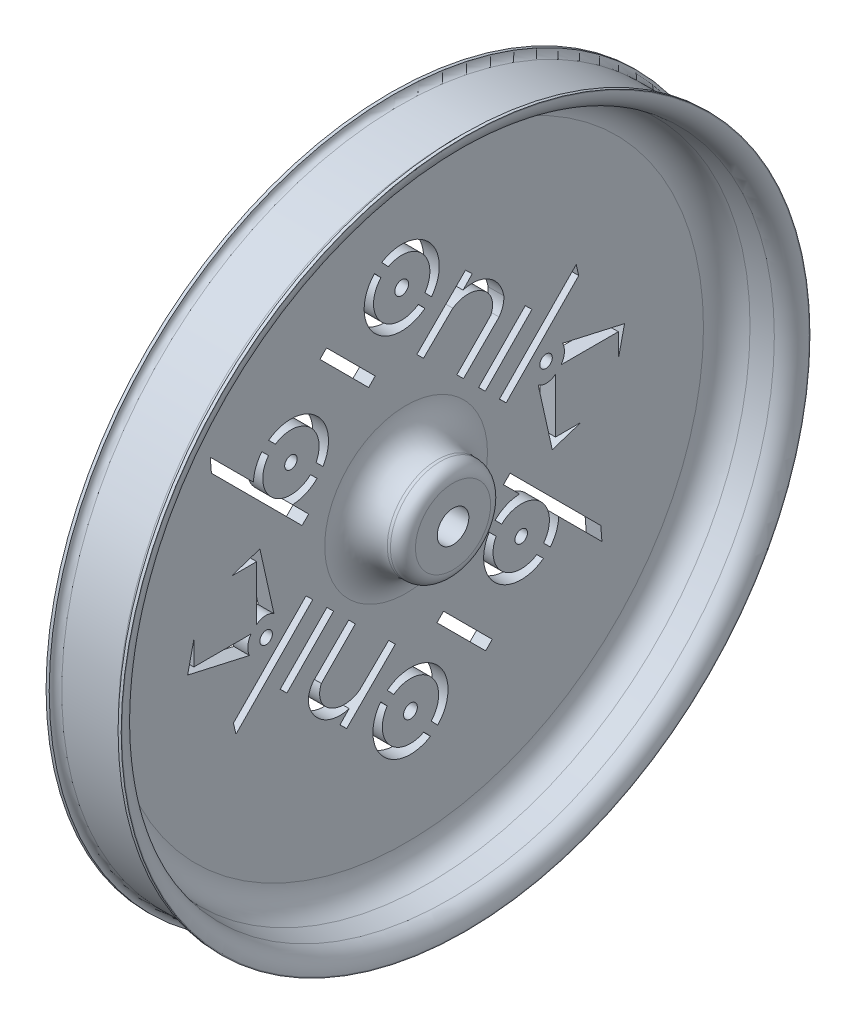
SolidWorks part; units mm, degrees
ref_plane "Płaszczyzna przednia" through (0, 0, 0) normal (0, 0, 1) x (1, 0, 0)
ref_plane "Płaszczyzna górna" through (0, 0, 0) normal (0, 1, 0) x (1, 0, 0)
ref_plane "Płaszczyzna prawa" through (0, 0, 0) normal (1, 0, 0) x (0, 0, -1)
sketch "Szkic1" plane through (0, 0, 0) normal (0, 0, 1) x (1, 0, 0)
  line L0 (7.5, -25.7789) -> (-2.5, -25.7789)
  line L1 (7.5, -25.7789) -> (7.5, -17.7789)
  line L2 (7.5, -17.7789) -> (0, -17.7789)
  line L3 (0, -17.7789) -> (0, 21.719)
  line L4 (-2.5, 29.2211) -> (-2, 29.2211)
  line L5 (9.5, 29.2211) -> (9.5, 29.1143)
  line L6 (9.5, 29.2211) -> (9, 29.2211)
  line L7 (-2, 29.2211) -> (-2, 29.2183)
  line L8 (-1, 28.2183) -> (8, 28.2183)
  line L9 (-2.5, 29.2211) -> (-2.5, -25.7789)
  line L10 (3.4713, 25.6839) -> (6.8965, 26.1406)
  line L11 (9, 29.2183) -> (9, 29.2211)
  arc A0 (-1, 28.2183) -> (-2, 29.2183) centre (-1, 29.2183) cw
  arc A1 (9.5, 29.1143) -> (6.8965, 26.1406) centre (6.5, 29.1143) cw
  arc A2 (0, 21.719) -> (3.4713, 25.6839) centre (4, 21.719) cw
  arc A3 (8, 28.2183) -> (9, 29.2183) centre (8, 29.2183) ccw
  point P10 (9.5, 26.2211)
  point P17 (0, 27.2211)
  dimension "D6" = 0.5
  dimension "D9" = 3
  dimension "D10" = 4
  dimension "D12" = 1
  dimension "D1" = 10
  dimension "D2" = 8
  dimension "D3" = 55
  dimension "D4" = 12
  dimension "D5" = 3
  dimension "D7" = 0.5
  dimension "D8" = 45
  dimension "D11" = 2.5
revolve "Obrót1" add sketch "Szkic1" angle 360 about L0
sketch "Szkic4" plane through (7.5, 0, 0) normal (1, 0, 0) x (0, 0, -1)
  circle A0 centre (0, -25.7789) radius 2.525
  dimension "D1" = 5.05
extrude "Wytnij-wyciągnięcie8" cut sketch "Szkic4" against normal through all
sketch "Szkic5" plane through (0, 0, 0) normal (1, 0, 0) x (0, 0, -1)
  line L0 (112.1629, 275.1146) -> (679.4962, 275.1146) construction
  line L1 (-31.0948, -6.6131) -> (-16.6157, -21.0922)
  line L2 (-16.6157, -21.0922) -> (-15.5551, -20.0316)
  line L3 (-15.5551, -20.0316) -> (-18.1257, -17.4609)
  line L4 (-24.3831, -11.2036) -> (-31.2774, -4.3092)
  line L5 (-31.2774, -4.3092) -> (-31.0948, -6.6131)
  line L6 (-13.7626, 0.4627) -> (-12.702, 1.5234)
  line L7 (-12.702, 1.5234) -> (-4.9238, -6.2548)
  line L8 (-4.9238, -6.2548) -> (-5.9844, -7.3154)
  line L9 (-5.9844, -7.3154) -> (-13.7626, 0.4627)
  line L10 (2.7778, -7.6585) -> (1.7172, -6.5979)
  line L11 (1.7172, -6.5979) -> (9.4953, 1.1803)
  line L12 (9.4953, 1.1803) -> (10.57, 0.1339)
  line L13 (10.57, 0.1339) -> (9.0927, -1.3833)
  line L14 (2.7778, -7.6585) -> (7.4664, -3.0724)
  line L15 (14.8516, -7.9843) -> (9.168, -13.6679)
  line L16 (9.168, -13.6679) -> (8.1073, -12.6072)
  line L17 (8.1073, -12.6072) -> (13.5313, -7.0832)
  line L18 (19.0342, -8.5077) -> (20.1045, -9.5586)
  line L19 (20.1045, -9.5586) -> (12.6512, -17.1495)
  line L20 (12.6512, -17.1495) -> (11.5808, -16.0986)
  line L21 (11.5808, -16.0986) -> (19.0342, -8.5077)
  line L22 (14.91, -19.3675) -> (27.173, -6.8781)
  line L23 (27.173, -6.8781) -> (27.5713, -8.6134)
  line L24 (27.5713, -8.6134) -> (15.9803, -20.4184)
  line L25 (15.9803, -20.4184) -> (14.91, -19.3675)
  line L30 (25.0179, -16.6923) -> (34.8909, -18.9183)
  line L31 (34.8909, -18.9183) -> (33.8934, -23.3427)
  line L32 (33.8934, -23.3427) -> (33.8934, -19.5403)
  line L33 (33.8934, -19.5403) -> (24.7607, -19.5403)
  line L34 (21.1025, -20.5215) -> (23.3499, -30.5953)
  line L35 (23.3499, -30.5953) -> (27.9255, -29.0986)
  line L36 (27.9255, -29.0986) -> (23.865, -29.0986)
  line L37 (23.865, -29.0986) -> (23.865, -20.3921)
  line L38 (-14.2148, -15.7768) -> (-15.2757, -14.716)
  line L39 (-13.2714, -14.599) -> (-14.3731, -13.4973)
  line L40 (-21.9663, -8.7368) -> (-23.0341, -7.669)
  line L41 (-20.8696, -7.7122) -> (-21.9465, -6.6352)
  line L42 (-2.824, 7.8162) -> (-3.8882, 8.9319)
  line L43 (-4.0153, 6.8919) -> (-5.0523, 7.9791)
  line L44 (3.009, 1.3009) -> (4.0611, 0.1978)
  line L45 (1.9645, 0.2227) -> (3.0062, -0.8694)
  arc A0 (-2.824, 7.8162) -> (3.009, 1.3009) centre (-0.7, 3.8491) cw
  circle A1 centre (-18.3888, -11.4667) radius 1
  arc A2 (-4.0153, 6.8919) -> (1.9645, 0.2227) centre (-0.7, 3.8491) ccw
  circle A3 centre (-0.7, 3.8491) radius 1.1
  arc A6 (7.4664, -3.0724) -> (12.8569, -3.5397) centre (9.8742, -6.6212) cw
  arc A7 (9.0927, -1.3833) -> (15.6101, -5.4316) centre (10.5698, -6.2757) cw
  arc A8 (12.8569, -3.5397) -> (13.5313, -7.0832) centre (10.6785, -5.7902) cw
  arc A9 (15.6101, -5.4316) -> (14.8516, -7.9843) centre (11.6962, -5.6576) cw
  circle A10 centre (22.3514, -17.8482) radius 1
  arc A11 (25.0179, -16.6923) -> (24.7607, -19.5403) centre (22.4645, -17.8973) cw
  arc A12 (23.865, -20.3921) -> (21.1025, -20.5215) centre (22.3975, -18.6134) cw
  arc A13 (-23.0341, -7.669) -> (-24.3831, -11.2036) centre (-18.3888, -11.4667) ccw
  arc A14 (-21.9465, -6.6352) -> (-13.2714, -14.599) centre (-18.3888, -11.4667) cw
  arc A15 (-14.3731, -13.4973) -> (-20.8696, -7.7122) centre (-18.3888, -11.4667) ccw
  arc A16 (-21.9663, -8.7368) -> (-15.2757, -14.716) centre (-18.3888, -11.4667) ccw
  arc A17 (-14.2148, -15.7768) -> (-18.1257, -17.4609) centre (-18.3888, -11.4667) cw
  arc A18 (-3.8882, 8.9319) -> (4.0611, 0.1978) centre (-0.7, 3.8491) cw
  arc A19 (-5.0523, 7.9791) -> (3.0062, -0.8694) centre (-0.7, 3.8491) ccw
  point P71 (-1, -15)
  dimension "D11" = 1.5
  dimension "D12" = 2
  dimension "D13" = 2
  dimension "D14" = 1.5
  dimension "D15" = 1.5
  dimension "D19" = 11
  dimension "D23" = 1.5
  dimension "D24" = 1.5
  dimension "D25" = 6
  dimension "D26" = 6
  dimension "D1" = 1.5
  dimension "D2" = 1.5
  dimension "D5" = 1.5
  dimension "D6" = 1.5
  dimension "D7" = 1.5
  dimension "D8" = 1.5
  dimension "D9" = 1.5
  dimension "D10" = 1.5
  dimension "D16" = 1.5
  dimension "D17" = 1.5
  dimension "D18" = 1.5
  dimension "D20" = 11
  dimension "D21" = 10.6384
  dimension "D22" = 1.5
  dimension "D27" = 0.524
extrude "Wytnij-wyciągnięcie9" cut sketch "Szkic5" against normal through all
fillet "Zaokrąglenie1" radius 2 1 edges at (7.5, -25.7789, -8)
sketch "Szkic6" plane through (0, 0, 0) normal (1, 0, 0) x (0, 0, -1)
  line L35 (-20.6685, -60.7541) -> (-20.6685, -65.2374)
  line L36 (-20.6685, -65.2374) -> (-19.6852, -65.2374)
  line L37 (-19.6852, -65.2374) -> (-19.6852, -62.7584)
  line L38 (-19.729, -61.5951) -> (-19.6986, -61.5951)
  line L39 (-19.5465, -62.2204) -> (-18.3908, -65.2374)
  line L40 (-18.3908, -65.2374) -> (-17.4985, -65.2374)
  line L41 (-17.4985, -65.2374) -> (-16.3631, -62.1893)
  line L42 (-16.211, -61.5951) -> (-16.184, -61.5951)
  line L43 (-16.2244, -62.5549) -> (-16.2244, -65.2374)
  line L44 (-16.2244, -65.2374) -> (-15.1462, -65.2374)
  line L45 (-15.1462, -65.2374) -> (-15.1462, -60.7541)
  line L46 (-15.1462, -60.7541) -> (-16.7043, -60.7541)
  line L47 (-16.7043, -60.7541) -> (-17.6946, -63.4053)
  line L48 (-17.8871, -64.0525) -> (-17.9075, -64.0525)
  line L49 (-18.08, -63.4117) -> (-19.0699, -60.7541)
  line L50 (-19.0699, -60.7541) -> (-20.6685, -60.7541)
  line L51 (-12.801, -60.7541) -> (-14.565, -65.2374)
  line L52 (-14.565, -65.2374) -> (-13.3822, -65.2374)
  line L53 (-13.3822, -65.2374) -> (-13.041, -64.2401)
  line L54 (-13.041, -64.2401) -> (-11.3174, -64.2401)
  line L55 (-11.3174, -64.2401) -> (-10.9726, -65.2374)
  line L56 (-10.9726, -65.2374) -> (-9.7831, -65.2374)
  line L57 (-9.7831, -65.2374) -> (-11.5066, -60.7541)
  line L58 (-11.5066, -60.7541) -> (-12.801, -60.7541)
  line L59 (-8.7022, -60.7541) -> (-7.2894, -62.9959)
  line L60 (-7.2894, -62.9959) -> (-8.8338, -65.2374)
  line L61 (-8.8338, -65.2374) -> (-7.5327, -65.2374)
  line L62 (-7.5327, -65.2374) -> (-6.6945, -63.79)
  line L63 (-6.5829, -63.4774) -> (-6.5695, -63.4774)
  line L64 (-6.4716, -63.7776) -> (-5.6367, -65.2374)
  line L65 (-5.6367, -65.2374) -> (-4.3423, -65.2374)
  line L66 (-4.3423, -65.2374) -> (-5.8363, -62.9771)
  line L67 (-5.8363, -62.9771) -> (-4.3828, -60.7541)
  line L68 (-4.3828, -60.7541) -> (-5.5996, -60.7541)
  line L69 (-5.5996, -60.7541) -> (-6.37, -62.0859)
  line L70 (-6.5221, -62.4768) -> (-6.5358, -62.4768)
  line L71 (-6.6812, -62.0987) -> (-7.374, -60.7541)
  line L72 (-7.374, -60.7541) -> (-8.7022, -60.7541)
  line L73 (-2.5549, -60.7541) -> (-2.5549, -65.2374)
  line L74 (-2.5549, -65.2374) -> (-0.693, -65.2374)
  line L75 (-0.0506, -62.8302) -> (-0.0506, -62.8177)
  line L76 (-0.7909, -60.7541) -> (-2.5549, -60.7541)
  line L77 (4.4336, -60.7541) -> (2.6693, -65.2374)
  line L78 (2.6693, -65.2374) -> (3.8521, -65.2374)
  line L79 (3.8521, -65.2374) -> (4.1936, -64.2401)
  line L80 (4.1936, -64.2401) -> (5.9172, -64.2401)
  line L81 (5.9172, -64.2401) -> (6.2618, -65.2374)
  line L82 (6.2618, -65.2374) -> (7.4516, -65.2374)
  line L83 (7.4516, -65.2374) -> (5.728, -60.7541)
  line L84 (5.728, -60.7541) -> (4.4336, -60.7541)
  line L85 (8.877, -60.7541) -> (8.877, -63.3429)
  line L86 (12.8853, -63.2961) -> (12.8853, -60.7541)
  line L87 (12.8853, -60.7541) -> (11.7937, -60.7541)
  line L88 (11.7937, -60.7541) -> (11.7937, -63.3928)
  line L89 (9.9723, -63.3554) -> (9.9723, -60.7541)
  line L90 (9.9723, -60.7541) -> (8.877, -60.7541)
  line L91 (14.9702, -60.7541) -> (14.9702, -65.2374)
  line L92 (14.9702, -65.2374) -> (15.9537, -65.2374)
  line L93 (15.9537, -65.2374) -> (15.9537, -62.7584)
  line L94 (15.9096, -61.5951) -> (15.9401, -61.5951)
  line L95 (16.0921, -62.2204) -> (17.2482, -65.2374)
  line L96 (17.2482, -65.2374) -> (18.1402, -65.2374)
  line L97 (18.1402, -65.2374) -> (19.2759, -62.1893)
  line L98 (19.4279, -61.5951) -> (19.455, -61.5951)
  line L99 (19.4142, -62.5549) -> (19.4142, -65.2374)
  line L100 (19.4142, -65.2374) -> (20.4924, -65.2374)
  line L101 (20.4924, -65.2374) -> (20.4924, -60.7541)
  line L102 (20.4924, -60.7541) -> (18.9343, -60.7541)
  line L103 (18.9343, -60.7541) -> (17.9443, -63.4053)
  line L104 (17.7515, -64.0525) -> (17.7314, -64.0525)
  line L105 (17.559, -63.4117) -> (16.5687, -60.7541)
  line L106 (16.5687, -60.7541) -> (14.9702, -60.7541)
  line L107 (-1.4634, -61.4983) -> (-1.0546, -61.4983)
  line L108 (-0.9834, -62.5613) -> (-1.4634, -62.5613)
  line L109 (-1.4634, -62.5613) -> (-1.4634, -61.4983)
  line L110 (-12.1961, -61.5546) -> (-12.169, -61.5546)
  line L111 (-12.0878, -61.9579) -> (-11.5674, -63.4649)
  line L112 (-11.5674, -63.4649) -> (-12.8077, -63.4649)
  line L113 (-12.8077, -63.4649) -> (-12.2807, -61.9454)
  line L114 (5.0385, -61.5546) -> (5.0656, -61.5546)
  line L115 (5.1465, -61.9579) -> (5.6672, -63.4649)
  line L116 (5.6672, -63.4649) -> (4.4266, -63.4649)
  line L117 (4.4266, -63.4649) -> (4.954, -61.9454)
  line L118 (-1.4634, -63.3116) -> (-0.8651, -63.3116)
  line L119 (-0.8721, -64.4935) -> (-1.4634, -64.4935)
  line L120 (-1.4634, -64.4935) -> (-1.4634, -63.3116)
  spline S29 degree 3 poles (-19.6852, -62.7584) (-19.6863, -62.6412) (-19.6885, -62.3946) (-19.7038, -62.0067) (-19.7203, -61.7363) (-19.729, -61.5951) knots 0 0 0 0 0.302027 0.635343 1 1 1 1
  spline S30 degree 3 poles (-19.6986, -61.5951) (-19.6777, -61.6928) (-19.6418, -61.8605) (-19.5944, -62.07) (-19.5596, -62.1793) (-19.5465, -62.2204) knots 0 0 0 0 0.465921 0.79909 1 1 1 1
  spline S31 degree 3 poles (-16.3631, -62.1893) (-16.3469, -62.1406) (-16.3091, -62.0272) (-16.2606, -61.8282) (-16.2287, -61.6783) (-16.211, -61.5951) knots 0 0 0 0 0.250853 0.584012 1 1 1 1
  spline S32 degree 3 poles (-16.184, -61.5951) (-16.192, -61.7084) (-16.2076, -61.9282) (-16.2215, -62.2483) (-16.2235, -62.455) (-16.2244, -62.5549) knots 0 0 0 0 0.354704 0.68797 1 1 1 1
  spline S33 degree 3 poles (-17.6946, -63.4053) (-17.7173, -63.4698) (-17.7649, -63.6052) (-17.8284, -63.8213) (-17.867, -63.9733) (-17.8871, -64.0525) knots 0 0 0 0 0.303823 0.637003 1 1 1 1
  spline S34 degree 3 poles (-17.9075, -64.0525) (-17.921, -63.9809) (-17.9481, -63.8368) (-18.006, -63.6226) (-18.0552, -63.4824) (-18.08, -63.4117) knots 0 0 0 0 0.329002 0.661877 1 1 1 1
  spline S35 degree 3 poles (-6.6945, -63.79) (-6.6771, -63.7475) (-6.6457, -63.6709) (-6.6071, -63.5669) (-6.5902, -63.5043) (-6.5829, -63.4774) knots 0 0 0 0 0.414756 0.747814 1 1 1 1
  spline S36 degree 3 poles (-6.5695, -63.4774) (-6.5588, -63.521) (-6.5398, -63.5987) (-6.5093, -63.7001) (-6.4828, -63.7546) (-6.4716, -63.7776) knots 0 0 0 0 0.425946 0.758455 1 1 1 1
  spline S37 degree 3 poles (-6.37, -62.0859) (-6.3924, -62.1388) (-6.4329, -62.2345) (-6.4846, -62.3645) (-6.5107, -62.4427) (-6.5221, -62.4768) knots 0 0 0 0 0.410263 0.743484 1 1 1 1
  spline S38 degree 3 poles (-6.5358, -62.4768) (-6.5502, -62.4302) (-6.5778, -62.3406) (-6.6259, -62.2141) (-6.6632, -62.1361) (-6.6812, -62.0987) knots 0 0 0 0 0.360592 0.693428 1 1 1 1
  spline S39 degree 3 poles (-0.693, -65.2374) (-0.5222, -65.2304) (-0.2015, -65.2172) (0.2487, -65.1035) (0.4922, -64.9507) (0.6081, -64.8779) knots 0 0 0 0 0.373882 0.702052 1 1 1 1
  spline S40 degree 3 poles (0.6081, -64.8779) (0.7033, -64.7935) (0.8897, -64.6282) (1.0527, -64.2791) (1.0983, -63.9384) (1.0635, -63.6326) (0.9571, -63.3815) (0.8359, -63.2505) (0.7739, -63.1836) knots 0 0 0 0 0.196043 0.384151 0.584354 0.724031 0.858939 1 1 1 1
  spline S41 degree 3 poles (0.7739, -63.1836) (0.7003, -63.1231) (0.5494, -62.999) (0.264, -62.8813) (0.0574, -62.8477) (-0.0506, -62.8302) knots 0 0 0 0 0.312152 0.640149 1 1 1 1
  spline S42 degree 3 poles (-0.0506, -62.8177) (0.0366, -62.791) (0.2062, -62.739) (0.4375, -62.6115) (0.5631, -62.4963) (0.6252, -62.4393) knots 0 0 0 0 0.348857 0.67836 1 1 1 1
  spline S43 degree 3 poles (0.6252, -62.4393) (0.6783, -62.3781) (0.7819, -62.2587) (0.8732, -62.0373) (0.9041, -61.7787) (0.8637, -61.4951) (0.7078, -61.2193) (0.4508, -61.0073) (0.1088, -60.8572) (-0.3152, -60.7679) (-0.6241, -60.759) (-0.7909, -60.7541) knots 0 0 0 0 0.082794 0.161272 0.24114 0.347886 0.449253 0.558501 0.683554 0.829073 1 1 1 1
  spline S44 degree 3 poles (8.877, -63.3429) (8.902, -63.7261) (8.9478, -64.4281) (9.7681, -65.2358) (10.8627, -65.3596) (11.9652, -65.2343) (12.8118, -64.4089) (12.8594, -63.6886) (12.8853, -63.2961) knots 0 0 0 0 0.174138 0.319064 0.493285 0.672816 0.82168 1 1 1 1
  spline S45 degree 3 poles (11.7937, -63.3928) (11.7841, -63.594) (11.7669, -63.9521) (11.4054, -64.3907) (10.888, -64.4718) (10.3655, -64.3877) (9.9991, -63.9327) (9.9819, -63.5635) (9.9723, -63.3554) knots 0 0 0 0 0.186157 0.331278 0.493092 0.658063 0.807295 1 1 1 1
  spline S46 degree 3 poles (15.9537, -62.7584) (15.9527, -62.6412) (15.9504, -62.3946) (15.9349, -62.0067) (15.9183, -61.7363) (15.9096, -61.5951) knots 0 0 0 0 0.302025 0.635343 1 1 1 1
  spline S47 degree 3 poles (15.9401, -61.5951) (15.961, -61.6928) (15.9969, -61.8605) (16.0442, -62.07) (16.079, -62.1793) (16.0921, -62.2204) knots 0 0 0 0 0.465921 0.79909 1 1 1 1
  spline S48 degree 3 poles (19.2759, -62.1893) (19.2921, -62.1406) (19.3298, -62.0272) (19.3784, -61.8282) (19.4102, -61.6783) (19.4279, -61.5951) knots 0 0 0 0 0.250853 0.584012 1 1 1 1
  spline S49 degree 3 poles (19.455, -61.5951) (19.4469, -61.7084) (19.4313, -61.9282) (19.4172, -62.2483) (19.4152, -62.455) (19.4142, -62.5549) knots 0 0 0 0 0.354705 0.687973 1 1 1 1
  spline S50 degree 3 poles (17.9443, -63.4053) (17.9216, -63.4698) (17.874, -63.6052) (17.8103, -63.8213) (17.7717, -63.9733) (17.7515, -64.0525) knots 0 0 0 0 0.303822 0.63702 1 1 1 1
  spline S51 degree 3 poles (17.7314, -64.0525) (17.718, -63.9809) (17.6908, -63.8368) (17.633, -63.6226) (17.5838, -63.4824) (17.559, -63.4117) knots 0 0 0 0 0.329002 0.661877 1 1 1 1
  spline S52 degree 3 poles (-1.0546, -61.4983) (-0.9058, -61.5032) (-0.6527, -61.5115) (-0.3168, -61.6834) (-0.2429, -61.9528) (-0.2697, -62.1549) (-0.3374, -62.3027) (-0.4507, -62.4192) (-0.6, -62.5033) (-0.782, -62.5535) (-0.9134, -62.5586) (-0.9834, -62.5613) knots 0 0 0 0 0.214019 0.36393 0.502152 0.581744 0.655624 0.731407 0.811388 0.899454 1 1 1 1
  spline S53 degree 3 poles (-12.169, -61.5546) (-12.1632, -61.6044) (-12.1519, -61.6995) (-12.1256, -61.8346) (-12.1, -61.9181) (-12.0878, -61.9579) knots 0 0 0 0 0.364666 0.697373 1 1 1 1
  spline S54 degree 3 poles (-12.2807, -61.9454) (-12.2668, -61.9024) (-12.2393, -61.8172) (-12.2108, -61.6863) (-12.201, -61.5984) (-12.1961, -61.5546) knots 0 0 0 0 0.337951 0.670517 1 1 1 1
  spline S55 degree 3 poles (5.0656, -61.5546) (5.0714, -61.6044) (5.0826, -61.6995) (5.1088, -61.8346) (5.1343, -61.9181) (5.1465, -61.9579) knots 0 0 0 0 0.364696 0.697382 1 1 1 1
  spline S56 degree 3 poles (4.954, -61.9454) (4.9678, -61.9024) (4.9953, -61.8172) (5.0238, -61.6863) (5.0336, -61.5984) (5.0385, -61.5546) knots 0 0 0 0 0.337951 0.670517 1 1 1 1
  spline S57 degree 3 poles (-0.8651, -63.3116) (-0.787, -63.3144) (-0.6412, -63.3195) (-0.44, -63.3699) (-0.2768, -63.4555) (-0.1528, -63.5721) (-0.0778, -63.7215) (-0.0572, -63.8897) (-0.0782, -64.0602) (-0.1538, -64.2168) (-0.2794, -64.34) (-0.4443, -64.4311) (-0.6472, -64.4851) (-0.7938, -64.4906) (-0.8721, -64.4935) knots 0 0 0 0 0.104446 0.194774 0.274999 0.348588 0.41889 0.493869 0.572366 0.645747 0.721977 0.804087 0.89532 1 1 1 1
sketch "Szkic7" plane through (0, 0, 0) normal (1, 0, 0) x (0, 0, -1)
  line L0 (-17.4603, -58.4263) -> (-17.4603, -54.0791)
  line L1 (-16.7503, -53.4132) -> (-14.2301, -54.0581)
  line L2 (-13.7698, -54.7242) -> (-13.7698, -54.7641)
  line L3 (-12.8433, -55.7872) -> (-6.3839, -55.7872)
  line L4 (-5.8713, -53.9113) -> (-8.3671, -52.0829)
  line L5 (-8.8797, -51.9124) -> (-11.4373, -51.9124)
  line L6 (-12.0226, -51.2308) -> (-12.0226, -49.2733)
  line L7 (-11.4373, -48.5916) -> (-8.8797, -48.5916)
  line L8 (-8.3671, -48.421) -> (-5.8713, -46.5928)
  line L9 (-6.3839, -44.7169) -> (-12.8433, -44.7169)
  line L10 (-13.7698, -45.7401) -> (-13.7698, -45.7801)
  line L11 (-14.2301, -46.446) -> (-16.7503, -47.0909)
  line L12 (-17.4603, -46.4248) -> (-17.4603, -42.0778)
  line L13 (-16.8751, -41.396) -> (-2.3518, -41.396)
  line L14 (-1.7668, -42.0778) -> (-1.7668, -47.7836)
  line L15 (-2.1038, -48.401) -> (-3.8125, -49.3352)
  line L16 (-3.8125, -51.1689) -> (-2.1038, -52.1031)
  line L17 (-1.7668, -52.7203) -> (-1.7668, -58.4263)
  line L18 (-2.3518, -59.1081) -> (-16.8751, -59.1081)
  line L25 (12.5072, -46.2896) -> (11.043, -45.1383)
  line L26 (0.5889, -41.2253) -> (6.712, -41.2253)
  line L27 (3.9645, -46.0591) -> (3.9645, -54.4452)
  line L28 (8.9311, -41.2253) -> (11.5375, -41.2253)
  line L29 (12.9545, -54.4452) -> (12.9545, -47.2104)
  line L30 (-0.5824, -58.1073) -> (-0.5824, -42.3968)
  line L31 (8.9311, -44.8876) -> (10.3191, -44.8876)
  line L32 (12.263, -41.4772) -> (17.0556, -45.2579)
  line L33 (17.5015, -46.1776) -> (17.5015, -58.1073)
  line L34 (5.136, -44.8876) -> (6.712, -44.8876)
  line L35 (6.712, -41.2253) -> (6.712, -44.8876)
  line L36 (8.9311, -41.2253) -> (8.9311, -44.8876)
  line L37 (6.712, -55.6165) -> (6.712, -59.2788)
  line L38 (8.9311, -55.6165) -> (8.9311, -59.2788)
  line L39 (5.136, -55.6165) -> (6.712, -55.6165)
  line L40 (8.9311, -55.6165) -> (11.7831, -55.6165)
  line L41 (16.3301, -59.2788) -> (8.9311, -59.2788)
  line L42 (6.712, -59.2788) -> (0.5889, -59.2788)
  spline S0 degree 3 poles (-16.8751, -59.1081) (-16.9789, -59.0879) (-17.1908, -59.0468) (-17.4157, -58.7696) (-17.445, -58.5441) (-17.4603, -58.4263) knots 0 0 0 0 0.314204 0.64159 1 1 1 1
  spline S1 degree 3 poles (-17.4603, -54.0791) (-17.445, -53.9603) (-17.4158, -53.7331) (-17.1921, -53.4681) (-16.9656, -53.3923) (-16.8345, -53.3983) (-16.7921, -53.4035) (-16.7643, -53.41) (-16.7503, -53.4132) knots 0 0 0 0 0.317625 0.607402 0.885007 0.922973 0.961318 1 1 1 1
  spline S2 degree 3 poles (-14.2301, -54.0581) (-14.1457, -54.0952) (-13.9729, -54.1712) (-13.8045, -54.4258) (-13.7816, -54.6226) (-13.7698, -54.7242) knots 0 0 0 0 0.315646 0.646724 1 1 1 1
  spline S3 degree 3 poles (-13.7698, -54.7641) (-13.7452, -54.9417) (-13.6975, -55.285) (-13.3367, -55.6982) (-13.0069, -55.7577) (-12.8433, -55.7872) knots 0 0 0 0 0.350775 0.677934 1 1 1 1
  spline S4 degree 3 poles (-6.3839, -55.7872) (-6.2194, -55.7577) (-5.888, -55.6982) (-5.5401, -55.2851) (-5.4303, -54.8291) (-5.4908, -54.432) (-5.6303, -54.1278) (-5.7914, -53.983) (-5.8713, -53.9113) knots 0 0 0 0 0.195604 0.394266 0.607256 0.741861 0.87198 1 1 1 1
  spline S5 degree 3 poles (-8.3671, -52.0829) (-8.4191, -52.0494) (-8.5221, -51.9829) (-8.698, -51.924) (-8.8191, -51.9162) (-8.8797, -51.9124) knots 0 0 0 0 0.337913 0.669074 1 1 1 1
  spline S6 degree 3 poles (-11.4373, -51.9124) (-11.541, -51.8922) (-11.753, -51.8511) (-11.978, -51.574) (-12.0073, -51.3486) (-12.0226, -51.2308) knots 0 0 0 0 0.31426 0.641681 1 1 1 1
  spline S7 degree 3 poles (-12.0226, -49.2733) (-12.0073, -49.1555) (-11.978, -48.93) (-11.753, -48.6529) (-11.541, -48.6117) (-11.4373, -48.5916) knots 0 0 0 0 0.35832 0.685765 1 1 1 1
  spline S8 degree 3 poles (-8.8797, -48.5916) (-8.8191, -48.5877) (-8.698, -48.58) (-8.5221, -48.5211) (-8.4191, -48.4546) (-8.3671, -48.421) knots 0 0 0 0 0.330905 0.662031 1 1 1 1
  spline S9 degree 3 poles (-5.8713, -46.5928) (-5.7914, -46.521) (-5.6304, -46.3762) (-5.4908, -46.0721) (-5.4303, -45.675) (-5.5401, -45.2191) (-5.8879, -44.8059) (-6.2194, -44.7464) (-6.3839, -44.7169) knots 0 0 0 0 0.128053 0.258158 0.392673 0.605714 0.804392 1 1 1 1
  spline S10 degree 3 poles (-12.8433, -44.7169) (-13.0069, -44.7464) (-13.3367, -44.8059) (-13.6976, -45.2192) (-13.7452, -45.5625) (-13.7698, -45.7401) knots 0 0 0 0 0.322035 0.649183 1 1 1 1
  spline S11 degree 3 poles (-13.7698, -45.7801) (-13.7816, -45.8816) (-13.8045, -46.0784) (-13.9729, -46.3329) (-14.1457, -46.4089) (-14.2301, -46.446) knots 0 0 0 0 0.353204 0.6843 1 1 1 1
  spline S12 degree 3 poles (-16.7503, -47.0909) (-16.7643, -47.0941) (-16.7921, -47.1004) (-16.8344, -47.1057) (-16.9119, -47.1091) (-17.0261, -47.0918) (-17.1652, -47.0254) (-17.2881, -46.9183) (-17.3846, -46.7764) (-17.4485, -46.6069) (-17.4563, -46.4862) (-17.4603, -46.4248) knots 0 0 0 0 0.038338 0.076325 0.113973 0.246125 0.380414 0.52179 0.677489 0.836012 1 1 1 1
  spline S13 degree 3 poles (-17.4603, -42.0778) (-17.445, -41.96) (-17.4157, -41.7345) (-17.1908, -41.4573) (-16.9789, -41.4162) (-16.8751, -41.396) knots 0 0 0 0 0.35841 0.685797 1 1 1 1
  spline S14 degree 3 poles (-2.3518, -41.396) (-2.248, -41.4162) (-2.0362, -41.4573) (-1.8113, -41.7345) (-1.7821, -41.96) (-1.7668, -42.0778) knots 0 0 0 0 0.314134 0.641538 1 1 1 1
  spline S15 degree 3 poles (-1.7668, -47.7836) (-1.7751, -47.8688) (-1.7913, -48.0352) (-1.9102, -48.2602) (-2.0402, -48.3547) (-2.1038, -48.401) knots 0 0 0 0 0.348556 0.680939 1 1 1 1
  spline S16 degree 3 poles (-3.8125, -49.3352) (-3.9108, -49.4046) (-4.1089, -49.5446) (-4.2857, -49.8785) (-4.3488, -50.252) (-4.2857, -50.6256) (-4.1089, -50.9595) (-3.9108, -51.0995) (-3.8125, -51.1689) knots 0 0 0 0 0.162555 0.327554 0.5 0.672446 0.837445 1 1 1 1
  spline S17 degree 3 poles (-2.1038, -52.1031) (-2.0402, -52.1494) (-1.9102, -52.2439) (-1.7914, -52.4688) (-1.7751, -52.6352) (-1.7668, -52.7203) knots 0 0 0 0 0.319126 0.651528 1 1 1 1
  spline S18 degree 3 poles (-1.7668, -58.4263) (-1.7821, -58.5441) (-1.8113, -58.7696) (-2.0362, -59.0468) (-2.248, -59.0879) (-2.3518, -59.1081) knots 0 0 0 0 0.358462 0.685866 1 1 1 1
  spline S19 degree 3 poles (11.043, -45.1383) (10.9713, -45.0891) (10.8282, -44.9912) (10.5788, -44.9049) (10.4059, -44.8934) (10.3191, -44.8876) knots 0 0 0 0 0.334028 0.666006 1 1 1 1
  spline S20 degree 3 poles (5.136, -44.8876) (4.9307, -44.9198) (4.5263, -44.9833) (4.0602, -45.4494) (3.9967, -45.8538) (3.9645, -46.0591) knots 0 0 0 0 0.336657 0.663343 1 1 1 1
  spline S21 degree 3 poles (3.9645, -54.4452) (3.9967, -54.6504) (4.0602, -55.0549) (4.5263, -55.5208) (4.9307, -55.5843) (5.136, -55.6165) knots 0 0 0 0 0.336654 0.663329 1 1 1 1
  spline S22 degree 3 poles (11.7831, -55.6165) (11.9883, -55.5843) (12.3928, -55.5208) (12.8588, -55.0549) (12.9223, -54.6504) (12.9545, -54.4452) knots 0 0 0 0 0.336671 0.663346 1 1 1 1
  spline S23 degree 3 poles (12.9545, -47.2104) (12.9439, -47.0926) (12.9227, -46.8582) (12.7644, -46.5323) (12.5932, -46.3708) (12.5072, -46.2896) knots 0 0 0 0 0.334581 0.665468 1 1 1 1
  spline S24 degree 3 poles (-0.5824, -42.3968) (-0.5502, -42.1915) (-0.4867, -41.7871) (-0.0208, -41.321) (0.3837, -41.2575) (0.5889, -41.2253) knots 0 0 0 0 0.336684 0.663379 1 1 1 1
  spline S25 degree 3 poles (11.5375, -41.2253) (11.6245, -41.2311) (11.798, -41.2427) (12.0478, -41.3295) (12.1912, -41.4278) (12.263, -41.4772) knots 0 0 0 0 0.334034 0.666034 1 1 1 1
  spline S26 degree 3 poles (17.0556, -45.2579) (17.1414, -45.3391) (17.312, -45.5006) (17.4697, -45.826) (17.4908, -46.06) (17.5015, -46.1776) knots 0 0 0 0 0.334553 0.665486 1 1 1 1
  spline S27 degree 3 poles (17.5015, -58.1073) (17.4692, -58.3126) (17.4057, -58.717) (16.9398, -59.1831) (16.5354, -59.2466) (16.3301, -59.2788) knots 0 0 0 0 0.336684 0.663379 1 1 1 1
  spline S28 degree 3 poles (0.5889, -59.2788) (0.3837, -59.2466) (-0.0208, -59.1831) (-0.4867, -58.717) (-0.5502, -58.3126) (-0.5824, -58.1073) knots 0 0 0 0 0.336621 0.663316 1 1 1 1
extrude "Dodanie-wyciągnięcie1" [suppressed] add sketch "Szkic6" along normal blind 0.8
extrude "Wytnij-wyciągnięcie10" [suppressed] cut sketch "Szkic7" against normal through all
fillet "Zaokrąglenie2" [suppressed] radius 0.15
fillet "Zaokrąglenie4" radius 5 1 edges at (0, -25.7789, -8) type face fillet first side face at (0, 1.9415, 2.8087) second side face at (5.5, -25.7789, -8)
pattern_circular "Szyk kołowy1" count 2 over 360 about axis through (-2.5, -25.7789, 0) along (1, 0, 0) of "Wytnij-wyciągnięcie9" reverse direction yes
